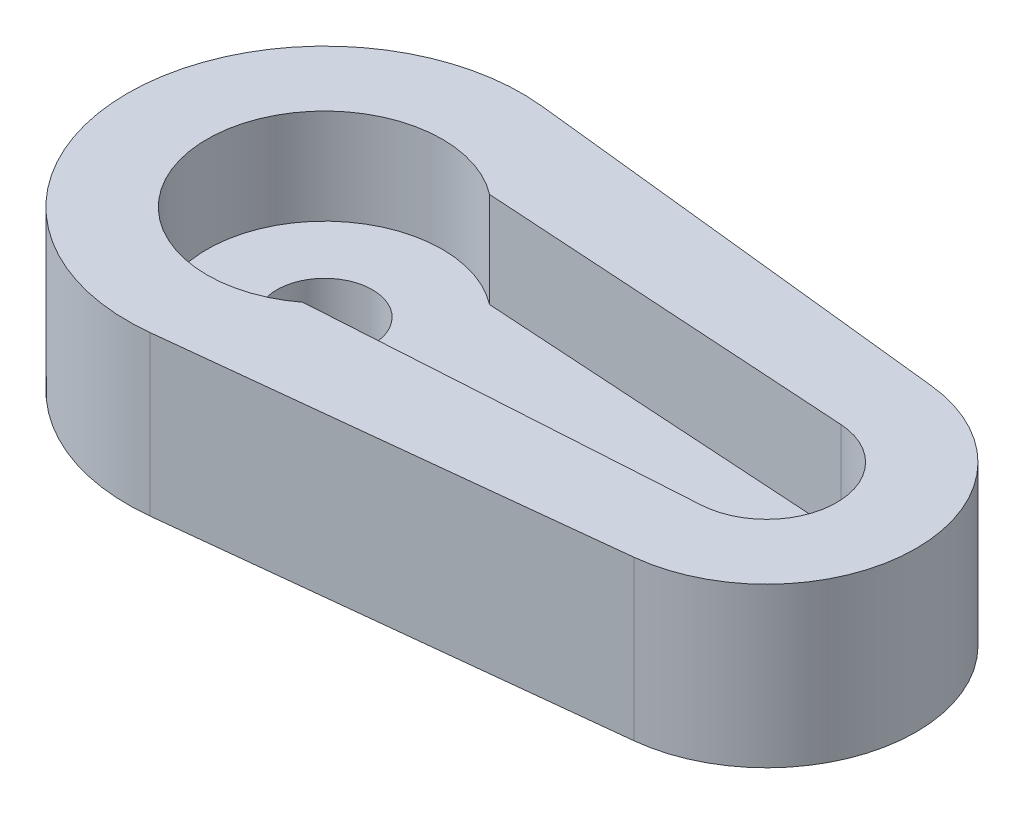
SolidWorks part; units mm, degrees
ref_plane "Front Plane" through (0, 0, 0) normal (0, 0, 1) x (1, 0, 0)
ref_plane "Top Plane" through (0, 0, 0) normal (0, 1, 0) x (1, 0, 0)
ref_plane "Right Plane" through (0, 0, 0) normal (1, 0, 0) x (0, 0, -1)
sketch "Sketch1" plane through (0, 0, 0) normal (0, 1, 0) x (1, 0, 0)
  line L0 (2.25, 2.9373) -> (14.0381, 2.1957)
  line L1 (2.25, -2.9373) -> (14.0381, -2.1957)
  line L2 (0.6691, 6.1638) -> (14.4072, 4.6726)
  line L3 (0.6691, -6.1638) -> (14.4072, -4.6726)
  circle A0 centre (0, 0) radius 1.5
  arc A1 (2.25, 2.9373) -> (2.25, -2.9373) centre (0, 0) ccw
  arc A2 (0.6691, 6.1638) -> (0.6691, -6.1638) centre (0, 0) ccw
  arc A3 (14.0381, -2.1957) -> (14.0381, 2.1957) centre (13.9, 0) ccw
  arc A4 (14.4072, -4.6726) -> (14.4072, 4.6726) centre (13.9, 0) ccw
  point P11 (16.1, 0)
  point P14 (-3.7, 0)
  dimension "D1" = 3
  dimension "D2" = 7.4
  dimension "D3" = 4.4
  dimension "D6" = 2.5
  dimension "D7" = 2.5
  dimension "D4" = 2.25
  dimension "D5" = 19.8
extrude "Boss-Extrude1" add sketch "Sketch1" along normal blind 2 contours L1 A3 L0 A1 A0 region at (5.7746, 0, 0)
extrude "Boss-Extrude2" add sketch "Sketch1<3>" along normal blind 5 contours L3 A4 L2 A2 A3 L1 A1 L0 region at (7.5082, 0, -5.1425)
sketch "Sketch1<3>" plane through (0, 0, 0) normal (0, 1, 0) x (1, 0, 0) same geometry as "Sketch1"
